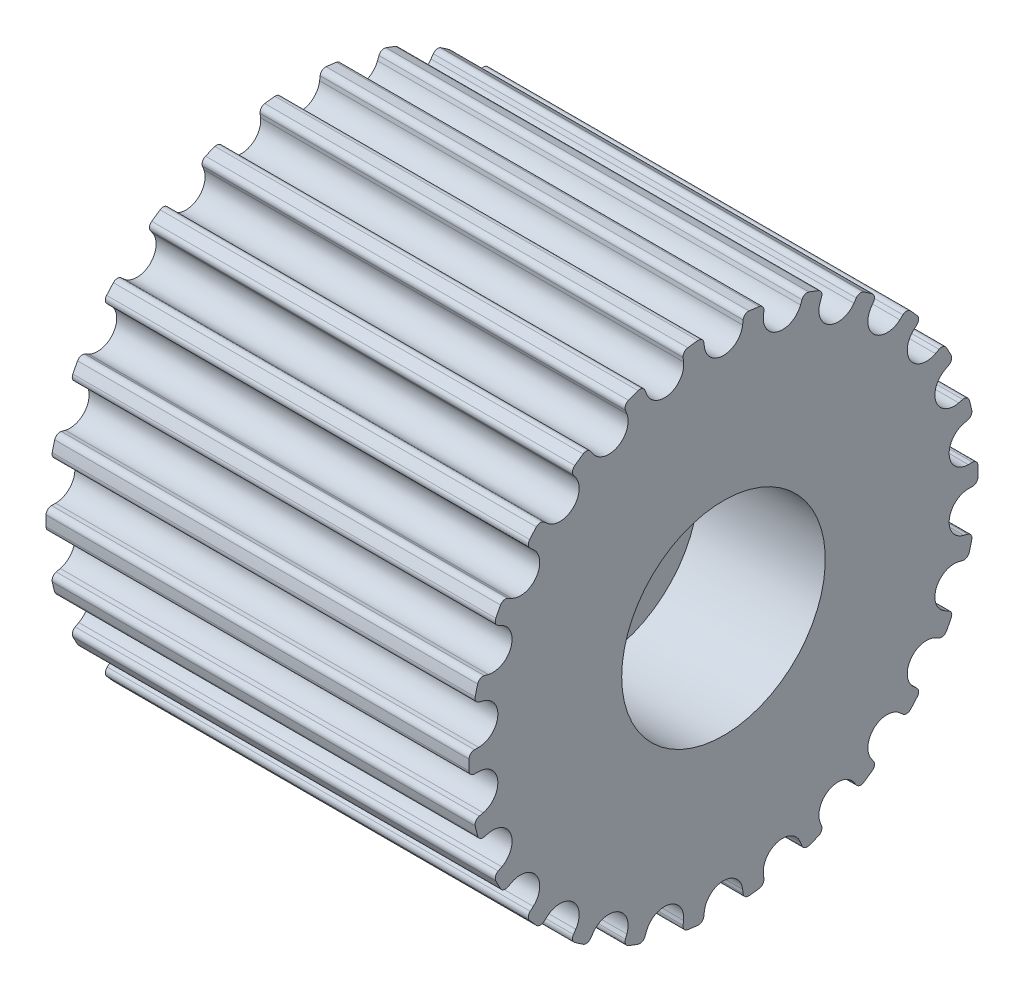
SolidWorks part; units mm, degrees
ref_plane "前视基准面" through (0, 0, 0) normal (0, 0, 1) x (1, 0, 0)
ref_plane "上视基准面" through (0, 0, 0) normal (0, 1, 0) x (1, 0, 0)
ref_plane "右视基准面" through (0, 0, 0) normal (1, 0, 0) x (0, 0, -1)
sketch "草图1" plane through (0, 0, 0) normal (0, 0, 1) x (1, 0, 0)
  line L0 (0, 0) -> (64.8368, 0) construction
  line L1 (0, 2.4068) -> (0, 12.034)
  line L2 (0, 12.034) -> (20, 12.034)
  line L3 (20, 12.034) -> (20, 4.8136)
  line L4 (20, 4.8136) -> (14, 4.8136)
  line L5 (14, 4.8136) -> (14, 2.4068)
  line L6 (14, 2.4068) -> (0, 2.4068)
  dimension "L" = 14
  dimension "B" = 20
  dimension "d" = 4.8136
  dimension "d1" = 9.6272
  dimension "da" = 24.068
revolve "旋转1" add sketch "草图1" angle 360 about L0
chamfer "倒角1" distance 1 angle 45 2 edges at (14, 0, 2.4068) (0, 0, 2.4068)
sketch "草图4" plane through (0, 0, 0) normal (-1, 0, 0) x (0, 0, 1)
  line L1 (-1, 2.1892) -> (1, 2.1892)
  line L2 (-1, 2.1892) -> (-1, 3.4068)
  line L3 (-1, 3.4068) -> (1, 3.4068)
  line L4 (1, 2.1892) -> (1, 3.4068)
  circle A0 centre (0, 0) radius 2.4068 construction
  point P6 (0, 3.4068)
  dimension "键槽高度" = 3.4068
  dimension "键槽宽度" = 2
  dimension "t1" = 1
extrude "切除-拉伸1" cut sketch "草图4" against normal through all
sketch "草图6" plane through (0, 0, 0) normal (1, 0, 0) x (0, 0, -1)
  line L0 (0, 0) -> (0, 30.6512) construction
  line L1 (0.9269, 11.7459) -> (0.9032, 11.5531)
  line L2 (1.4695, 11.9439) -> (1.6661, 13.5455)
  line L3 (-1.4695, 11.9439) -> (-1.6661, 13.5455)
  line L4 (-0.9269, 11.7459) -> (-0.9032, 11.5531)
  circle A0 centre (0, 0) radius 12.034 construction
  circle A1 centre (0, 0) radius 10.754 construction
  arc A2 (-0.9032, 11.5531) -> (0.9032, 11.5531) centre (0, 11.664) ccw
  arc A3 (1.6661, 13.5455) -> (-1.6661, 13.5455) centre (0, 0) ccw
  arc A4 (0.9269, 11.7459) -> (1.2111, 11.9729) centre (1.185, 11.7142) cw
  arc A5 (1.2111, 11.9729) -> (1.4695, 11.9439) centre (0, 0) cw
  arc A6 (-1.2111, 11.9729) -> (-1.4695, 11.9439) centre (0, 0) ccw
  arc A7 (-0.9269, 11.7459) -> (-1.2111, 11.9729) centre (-1.185, 11.7142) ccw
  point P7 (0, 1.9)
  point P8 (0, 29.3712)
  point P15 (0.9576, 11.9958)
  dimension "D1" = 21.508
  dimension "ra" = 0.26
  dimension "rf" = 0.91
  dimension "hg" = 1.28
  dimension "D3" = 0.26
  dimension "D4" = 1.6136
  dimension "angle" = 14
  dimension "bw" = 1.9
extrude "切除-拉伸2" cut sketch "草图6" along normal up to next
ref_axis "基准轴1" through (-1.4, 0, 0) along (1, 0, 0)
pattern_circular "阵列(圆周)3" count 26 over 360 about axis through (-1.4, 0, 0) along (1, 0, 0) of "切除-拉伸2"
equation "\"键槽高度@草图4\" = \"d@草图1\" / 2  + \"t1@草图4\""
equation "\"D1@草图6\" = \"da@草图1\"  - \"hg@草图6\" - \"hg@草图6\""
equation "\"D3@草图6\" = \"ra@草图6\""
